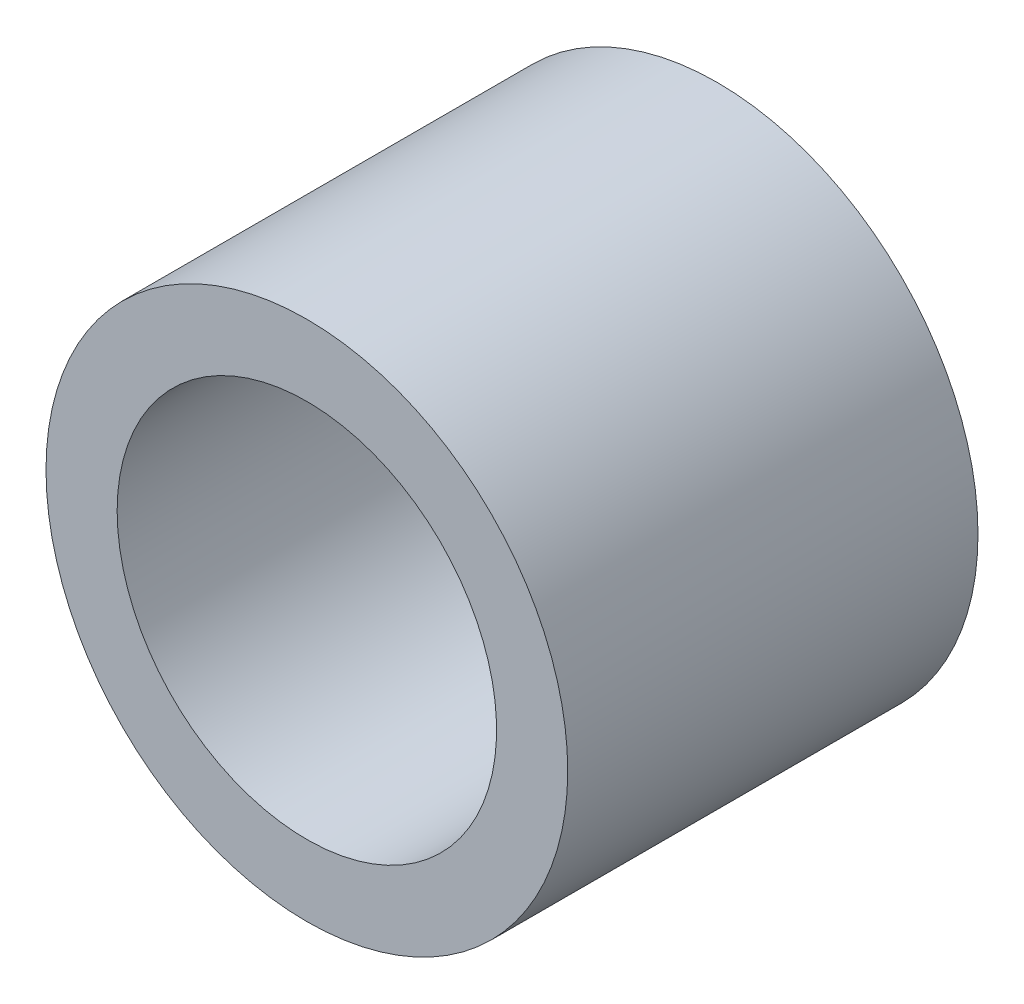
SolidWorks part; units mm, degrees
ref_plane "Front Plane" through (0, 0, 0) normal (0, 0, 1) x (1, 0, 0)
ref_plane "Top Plane" through (0, 0, 0) normal (0, 1, 0) x (1, 0, 0)
ref_plane "Right Plane" through (0, 0, 0) normal (1, 0, 0) x (0, 0, -1)
ref_plane "Plane1" through (0, 0, 12.7699) normal (0, 0, -1) x (-1, 0, 0)
sketch "Sketch1" plane through (0, 0, 12.7699) normal (0, 0, -1) x (-1, 0, 0)
  circle A0 centre (41.5529, -51.3213) radius 5.5
  circle A1 centre (41.5529, -51.3213) radius 17 construction
  circle A2 centre (41.5529, -51.3213) radius 4
  dimension "D1" = 11
  dimension "D2" = 8
extrude "Boss-Extrude1" add sketch "Sketch1" along normal up to surface (8.65 mm away)
